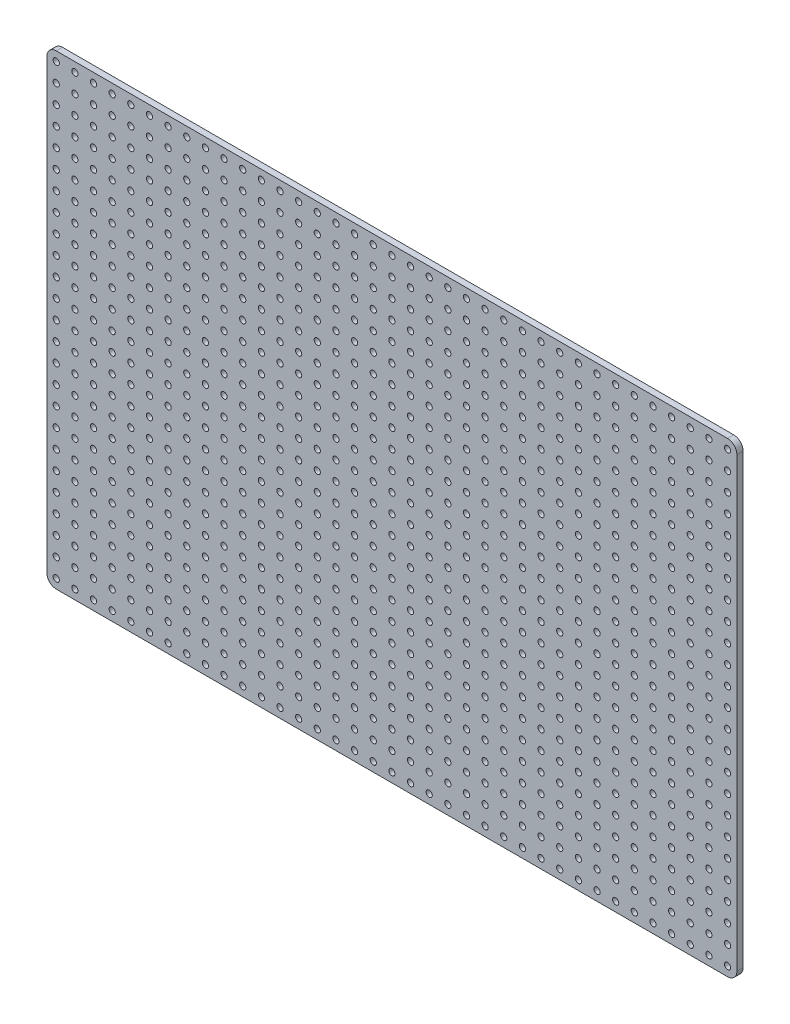
SolidWorks part; units mm, degrees
ref_plane "Alzado" through (0, 0, 0) normal (0, 0, 1) x (1, 0, 0)
ref_plane "Planta" through (0, 0, 0) normal (0, 1, 0) x (1, 0, 0)
ref_plane "Vista lateral" through (0, 0, 0) normal (1, 0, 0) x (0, 0, -1)
sketch "Model" plane through (0, 0, 0) normal (0, 0, 1) x (1, 0, 0)
  line L0 (256.4291, 471.7422) -> (580.4291, 471.7422)
  line L1 (256.4291, 246.7422) -> (580.4291, 246.7422)
  line L2 (251.9291, 251.2422) -> (251.9291, 467.2422)
  line L3 (584.9291, 467.2422) -> (584.9291, 251.2422)
  arc A0 (584.9291, 467.2422) -> (580.4291, 471.7422) centre (580.4291, 467.2422) ccw
  arc A1 (256.4291, 471.7422) -> (251.9291, 467.2422) centre (256.4291, 467.2422) ccw
  arc A2 (580.4291, 246.7422) -> (584.9291, 251.2422) centre (580.4291, 251.2422) ccw
  arc A3 (251.9291, 251.2422) -> (256.4291, 246.7422) centre (256.4291, 251.2422) ccw
  circle A4 centre (256.4291, 467.2422) radius 1.5
  circle A5 centre (256.4291, 458.2422) radius 1.5
  circle A6 centre (256.4291, 449.2422) radius 1.5
  circle A7 centre (256.4291, 440.2422) radius 1.5
  circle A8 centre (256.4291, 431.2422) radius 1.5
  circle A9 centre (256.4291, 422.2422) radius 1.5
  circle A10 centre (256.4291, 413.2422) radius 1.5
  circle A11 centre (256.4291, 404.2422) radius 1.5
  circle A12 centre (256.4291, 395.2422) radius 1.5
  circle A13 centre (256.4291, 386.2422) radius 1.5
  circle A14 centre (256.4291, 377.2422) radius 1.5
  circle A15 centre (256.4291, 368.2422) radius 1.5
  circle A16 centre (256.4291, 359.2422) radius 1.5
  circle A17 centre (256.4291, 350.2422) radius 1.5
  circle A18 centre (256.4291, 341.2422) radius 1.5
  circle A19 centre (256.4291, 332.2422) radius 1.5
  circle A20 centre (256.4291, 323.2422) radius 1.5
  circle A21 centre (256.4291, 314.2422) radius 1.5
  circle A22 centre (256.4291, 305.2422) radius 1.5
  circle A23 centre (265.4291, 467.2422) radius 1.5
  circle A24 centre (265.4291, 458.2422) radius 1.5
  circle A25 centre (265.4291, 449.2422) radius 1.5
  circle A26 centre (265.4291, 440.2422) radius 1.5
  circle A27 centre (265.4291, 431.2422) radius 1.5
  circle A28 centre (265.4291, 422.2422) radius 1.5
  circle A29 centre (265.4291, 413.2422) radius 1.5
  circle A30 centre (265.4291, 404.2422) radius 1.5
  circle A31 centre (265.4291, 395.2422) radius 1.5
  circle A32 centre (265.4291, 386.2422) radius 1.5
  circle A33 centre (265.4291, 377.2422) radius 1.5
  circle A34 centre (265.4291, 368.2422) radius 1.5
  circle A35 centre (265.4291, 359.2422) radius 1.5
  circle A36 centre (265.4291, 350.2422) radius 1.5
  circle A37 centre (265.4291, 341.2422) radius 1.5
  circle A38 centre (265.4291, 332.2422) radius 1.5
  circle A39 centre (265.4291, 323.2422) radius 1.5
  circle A40 centre (265.4291, 314.2422) radius 1.5
  circle A41 centre (265.4291, 305.2422) radius 1.5
  circle A42 centre (274.4291, 467.2422) radius 1.5
  circle A43 centre (274.4291, 458.2422) radius 1.5
  circle A44 centre (274.4291, 449.2422) radius 1.5
  circle A45 centre (274.4291, 440.2422) radius 1.5
  circle A46 centre (274.4291, 431.2422) radius 1.5
  circle A47 centre (274.4291, 422.2422) radius 1.5
  circle A48 centre (274.4291, 413.2422) radius 1.5
  circle A49 centre (274.4291, 404.2422) radius 1.5
  circle A50 centre (274.4291, 395.2422) radius 1.5
  circle A51 centre (274.4291, 386.2422) radius 1.5
  circle A52 centre (274.4291, 377.2422) radius 1.5
  circle A53 centre (274.4291, 368.2422) radius 1.5
  circle A54 centre (274.4291, 359.2422) radius 1.5
  circle A55 centre (274.4291, 350.2422) radius 1.5
  circle A56 centre (274.4291, 341.2422) radius 1.5
  circle A57 centre (274.4291, 332.2422) radius 1.5
  circle A58 centre (274.4291, 323.2422) radius 1.5
  circle A59 centre (274.4291, 314.2422) radius 1.5
  circle A60 centre (274.4291, 305.2422) radius 1.5
  circle A61 centre (283.4291, 467.2422) radius 1.5
  circle A62 centre (283.4291, 458.2422) radius 1.5
  circle A63 centre (283.4291, 449.2422) radius 1.5
  circle A64 centre (283.4291, 440.2422) radius 1.5
  circle A65 centre (283.4291, 431.2422) radius 1.5
  circle A66 centre (283.4291, 422.2422) radius 1.5
  circle A67 centre (283.4291, 413.2422) radius 1.5
  circle A68 centre (283.4291, 404.2422) radius 1.5
  circle A69 centre (283.4291, 395.2422) radius 1.5
  circle A70 centre (283.4291, 386.2422) radius 1.5
  circle A71 centre (283.4291, 377.2422) radius 1.5
  circle A72 centre (283.4291, 368.2422) radius 1.5
  circle A73 centre (283.4291, 359.2422) radius 1.5
  circle A74 centre (283.4291, 350.2422) radius 1.5
  circle A75 centre (283.4291, 341.2422) radius 1.5
  circle A76 centre (283.4291, 332.2422) radius 1.5
  circle A77 centre (283.4291, 323.2422) radius 1.5
  circle A78 centre (283.4291, 314.2422) radius 1.5
  circle A79 centre (283.4291, 305.2422) radius 1.5
  circle A80 centre (292.4291, 467.2422) radius 1.5
  circle A81 centre (292.4291, 458.2422) radius 1.5
  circle A82 centre (292.4291, 449.2422) radius 1.5
  circle A83 centre (292.4291, 440.2422) radius 1.5
  circle A84 centre (292.4291, 431.2422) radius 1.5
  circle A85 centre (292.4291, 422.2422) radius 1.5
  circle A86 centre (292.4291, 413.2422) radius 1.5
  circle A87 centre (292.4291, 404.2422) radius 1.5
  circle A88 centre (292.4291, 395.2422) radius 1.5
  circle A89 centre (292.4291, 386.2422) radius 1.5
  circle A90 centre (292.4291, 377.2422) radius 1.5
  circle A91 centre (292.4291, 368.2422) radius 1.5
  circle A92 centre (292.4291, 359.2422) radius 1.5
  circle A93 centre (292.4291, 350.2422) radius 1.5
  circle A94 centre (292.4291, 341.2422) radius 1.5
  circle A95 centre (292.4291, 332.2422) radius 1.5
  circle A96 centre (292.4291, 323.2422) radius 1.5
  circle A97 centre (292.4291, 314.2422) radius 1.5
  circle A98 centre (292.4291, 305.2422) radius 1.5
  circle A99 centre (301.4291, 467.2422) radius 1.5
  circle A100 centre (301.4291, 458.2422) radius 1.5
  circle A101 centre (301.4291, 449.2422) radius 1.5
  circle A102 centre (301.4291, 440.2422) radius 1.5
  circle A103 centre (301.4291, 431.2422) radius 1.5
  circle A104 centre (301.4291, 422.2422) radius 1.5
  circle A105 centre (301.4291, 413.2422) radius 1.5
  circle A106 centre (301.4291, 404.2422) radius 1.5
  circle A107 centre (301.4291, 395.2422) radius 1.5
  circle A108 centre (301.4291, 386.2422) radius 1.5
  circle A109 centre (301.4291, 377.2422) radius 1.5
  circle A110 centre (301.4291, 368.2422) radius 1.5
  circle A111 centre (301.4291, 359.2422) radius 1.5
  circle A112 centre (301.4291, 350.2422) radius 1.5
  circle A113 centre (301.4291, 341.2422) radius 1.5
  circle A114 centre (301.4291, 332.2422) radius 1.5
  circle A115 centre (301.4291, 323.2422) radius 1.5
  circle A116 centre (301.4291, 314.2422) radius 1.5
  circle A117 centre (301.4291, 305.2422) radius 1.5
  circle A118 centre (310.4291, 467.2422) radius 1.5
  circle A119 centre (310.4291, 458.2422) radius 1.5
  circle A120 centre (310.4291, 449.2422) radius 1.5
  circle A121 centre (310.4291, 440.2422) radius 1.5
  circle A122 centre (310.4291, 431.2422) radius 1.5
  circle A123 centre (310.4291, 422.2422) radius 1.5
  circle A124 centre (310.4291, 413.2422) radius 1.5
  circle A125 centre (310.4291, 404.2422) radius 1.5
  circle A126 centre (310.4291, 395.2422) radius 1.5
  circle A127 centre (310.4291, 386.2422) radius 1.5
  circle A128 centre (310.4291, 377.2422) radius 1.5
  circle A129 centre (310.4291, 368.2422) radius 1.5
  circle A130 centre (310.4291, 359.2422) radius 1.5
  circle A131 centre (310.4291, 350.2422) radius 1.5
  circle A132 centre (310.4291, 341.2422) radius 1.5
  circle A133 centre (310.4291, 332.2422) radius 1.5
  circle A134 centre (310.4291, 323.2422) radius 1.5
  circle A135 centre (310.4291, 314.2422) radius 1.5
  circle A136 centre (310.4291, 305.2422) radius 1.5
  circle A137 centre (319.4291, 467.2422) radius 1.5
  circle A138 centre (319.4291, 458.2422) radius 1.5
  circle A139 centre (319.4291, 449.2422) radius 1.5
  circle A140 centre (319.4291, 440.2422) radius 1.5
  circle A141 centre (319.4291, 431.2422) radius 1.5
  circle A142 centre (319.4291, 422.2422) radius 1.5
  circle A143 centre (319.4291, 413.2422) radius 1.5
  circle A144 centre (319.4291, 404.2422) radius 1.5
  circle A145 centre (319.4291, 395.2422) radius 1.5
  circle A146 centre (319.4291, 386.2422) radius 1.5
  circle A147 centre (319.4291, 377.2422) radius 1.5
  circle A148 centre (319.4291, 368.2422) radius 1.5
  circle A149 centre (319.4291, 359.2422) radius 1.5
  circle A150 centre (319.4291, 350.2422) radius 1.5
  circle A151 centre (319.4291, 341.2422) radius 1.5
  circle A152 centre (319.4291, 332.2422) radius 1.5
  circle A153 centre (319.4291, 323.2422) radius 1.5
  circle A154 centre (319.4291, 314.2422) radius 1.5
  circle A155 centre (319.4291, 305.2422) radius 1.5
  circle A156 centre (328.4291, 467.2422) radius 1.5
  circle A157 centre (328.4291, 458.2422) radius 1.5
  circle A158 centre (328.4291, 449.2422) radius 1.5
  circle A159 centre (328.4291, 440.2422) radius 1.5
  circle A160 centre (328.4291, 431.2422) radius 1.5
  circle A161 centre (328.4291, 422.2422) radius 1.5
  circle A162 centre (328.4291, 413.2422) radius 1.5
  circle A163 centre (328.4291, 404.2422) radius 1.5
  circle A164 centre (328.4291, 395.2422) radius 1.5
  circle A165 centre (328.4291, 386.2422) radius 1.5
  circle A166 centre (328.4291, 377.2422) radius 1.5
  circle A167 centre (328.4291, 368.2422) radius 1.5
  circle A168 centre (328.4291, 359.2422) radius 1.5
  circle A169 centre (328.4291, 350.2422) radius 1.5
  circle A170 centre (328.4291, 341.2422) radius 1.5
  circle A171 centre (328.4291, 332.2422) radius 1.5
  circle A172 centre (328.4291, 323.2422) radius 1.5
  circle A173 centre (328.4291, 314.2422) radius 1.5
  circle A174 centre (328.4291, 305.2422) radius 1.5
  circle A175 centre (337.4291, 467.2422) radius 1.5
  circle A176 centre (337.4291, 458.2422) radius 1.5
  circle A177 centre (337.4291, 449.2422) radius 1.5
  circle A178 centre (337.4291, 440.2422) radius 1.5
  circle A179 centre (337.4291, 431.2422) radius 1.5
  circle A180 centre (337.4291, 422.2422) radius 1.5
  circle A181 centre (337.4291, 413.2422) radius 1.5
  circle A182 centre (337.4291, 404.2422) radius 1.5
  circle A183 centre (337.4291, 395.2422) radius 1.5
  circle A184 centre (337.4291, 386.2422) radius 1.5
  circle A185 centre (337.4291, 377.2422) radius 1.5
  circle A186 centre (337.4291, 368.2422) radius 1.5
  circle A187 centre (337.4291, 359.2422) radius 1.5
  circle A188 centre (337.4291, 350.2422) radius 1.5
  circle A189 centre (337.4291, 341.2422) radius 1.5
  circle A190 centre (337.4291, 332.2422) radius 1.5
  circle A191 centre (337.4291, 323.2422) radius 1.5
  circle A192 centre (337.4291, 314.2422) radius 1.5
  circle A193 centre (337.4291, 305.2422) radius 1.5
  circle A194 centre (346.4291, 467.2422) radius 1.5
  circle A195 centre (346.4291, 458.2422) radius 1.5
  circle A196 centre (346.4291, 449.2422) radius 1.5
  circle A197 centre (346.4291, 440.2422) radius 1.5
  circle A198 centre (346.4291, 431.2422) radius 1.5
  circle A199 centre (346.4291, 422.2422) radius 1.5
  circle A200 centre (346.4291, 413.2422) radius 1.5
  circle A201 centre (346.4291, 404.2422) radius 1.5
  circle A202 centre (346.4291, 395.2422) radius 1.5
  circle A203 centre (346.4291, 386.2422) radius 1.5
  circle A204 centre (346.4291, 377.2422) radius 1.5
  circle A205 centre (346.4291, 368.2422) radius 1.5
  circle A206 centre (346.4291, 359.2422) radius 1.5
  circle A207 centre (346.4291, 350.2422) radius 1.5
  circle A208 centre (346.4291, 341.2422) radius 1.5
  circle A209 centre (346.4291, 332.2422) radius 1.5
  circle A210 centre (346.4291, 323.2422) radius 1.5
  circle A211 centre (346.4291, 314.2422) radius 1.5
  circle A212 centre (346.4291, 305.2422) radius 1.5
  circle A213 centre (355.4291, 467.2422) radius 1.5
  circle A214 centre (355.4291, 458.2422) radius 1.5
  circle A215 centre (355.4291, 449.2422) radius 1.5
  circle A216 centre (355.4291, 440.2422) radius 1.5
  circle A217 centre (355.4291, 431.2422) radius 1.5
  circle A218 centre (355.4291, 422.2422) radius 1.5
  circle A219 centre (355.4291, 413.2422) radius 1.5
  circle A220 centre (355.4291, 404.2422) radius 1.5
  circle A221 centre (355.4291, 395.2422) radius 1.5
  circle A222 centre (355.4291, 386.2422) radius 1.5
  circle A223 centre (355.4291, 377.2422) radius 1.5
  circle A224 centre (355.4291, 368.2422) radius 1.5
  circle A225 centre (355.4291, 359.2422) radius 1.5
  circle A226 centre (355.4291, 350.2422) radius 1.5
  circle A227 centre (355.4291, 341.2422) radius 1.5
  circle A228 centre (355.4291, 332.2422) radius 1.5
  circle A229 centre (355.4291, 323.2422) radius 1.5
  circle A230 centre (355.4291, 314.2422) radius 1.5
  circle A231 centre (355.4291, 305.2422) radius 1.5
  circle A232 centre (364.4291, 467.2422) radius 1.5
  circle A233 centre (364.4291, 458.2422) radius 1.5
  circle A234 centre (364.4291, 449.2422) radius 1.5
  circle A235 centre (364.4291, 440.2422) radius 1.5
  circle A236 centre (364.4291, 431.2422) radius 1.5
  circle A237 centre (364.4291, 422.2422) radius 1.5
  circle A238 centre (364.4291, 413.2422) radius 1.5
  circle A239 centre (364.4291, 404.2422) radius 1.5
  circle A240 centre (364.4291, 395.2422) radius 1.5
  circle A241 centre (364.4291, 386.2422) radius 1.5
  circle A242 centre (364.4291, 377.2422) radius 1.5
  circle A243 centre (364.4291, 368.2422) radius 1.5
  circle A244 centre (364.4291, 359.2422) radius 1.5
  circle A245 centre (364.4291, 350.2422) radius 1.5
  circle A246 centre (364.4291, 341.2422) radius 1.5
  circle A247 centre (364.4291, 332.2422) radius 1.5
  circle A248 centre (364.4291, 323.2422) radius 1.5
  circle A249 centre (364.4291, 314.2422) radius 1.5
  circle A250 centre (364.4291, 305.2422) radius 1.5
  circle A251 centre (373.4291, 467.2422) radius 1.5
  circle A252 centre (373.4291, 458.2422) radius 1.5
  circle A253 centre (373.4291, 449.2422) radius 1.5
  circle A254 centre (373.4291, 440.2422) radius 1.5
  circle A255 centre (373.4291, 431.2422) radius 1.5
  circle A256 centre (373.4291, 422.2422) radius 1.5
  circle A257 centre (373.4291, 413.2422) radius 1.5
  circle A258 centre (373.4291, 404.2422) radius 1.5
  circle A259 centre (373.4291, 395.2422) radius 1.5
  circle A260 centre (373.4291, 386.2422) radius 1.5
  circle A261 centre (373.4291, 377.2422) radius 1.5
  circle A262 centre (373.4291, 368.2422) radius 1.5
  circle A263 centre (373.4291, 359.2422) radius 1.5
  circle A264 centre (373.4291, 350.2422) radius 1.5
  circle A265 centre (373.4291, 341.2422) radius 1.5
  circle A266 centre (373.4291, 332.2422) radius 1.5
  circle A267 centre (373.4291, 323.2422) radius 1.5
  circle A268 centre (373.4291, 314.2422) radius 1.5
  circle A269 centre (373.4291, 305.2422) radius 1.5
  circle A270 centre (382.4291, 467.2422) radius 1.5
  circle A271 centre (382.4291, 458.2422) radius 1.5
  circle A272 centre (382.4291, 449.2422) radius 1.5
  circle A273 centre (382.4291, 440.2422) radius 1.5
  circle A274 centre (382.4291, 431.2422) radius 1.5
  circle A275 centre (382.4291, 422.2422) radius 1.5
  circle A276 centre (382.4291, 413.2422) radius 1.5
  circle A277 centre (382.4291, 404.2422) radius 1.5
  circle A278 centre (382.4291, 395.2422) radius 1.5
  circle A279 centre (382.4291, 386.2422) radius 1.5
  circle A280 centre (382.4291, 377.2422) radius 1.5
  circle A281 centre (382.4291, 368.2422) radius 1.5
  circle A282 centre (382.4291, 359.2422) radius 1.5
  circle A283 centre (382.4291, 350.2422) radius 1.5
  circle A284 centre (382.4291, 341.2422) radius 1.5
  circle A285 centre (382.4291, 332.2422) radius 1.5
  circle A286 centre (382.4291, 323.2422) radius 1.5
  circle A287 centre (382.4291, 314.2422) radius 1.5
  circle A288 centre (382.4291, 305.2422) radius 1.5
  circle A289 centre (391.4291, 467.2422) radius 1.5
  circle A290 centre (391.4291, 458.2422) radius 1.5
  circle A291 centre (391.4291, 449.2422) radius 1.5
  circle A292 centre (391.4291, 440.2422) radius 1.5
  circle A293 centre (391.4291, 431.2422) radius 1.5
  circle A294 centre (391.4291, 422.2422) radius 1.5
  circle A295 centre (391.4291, 413.2422) radius 1.5
  circle A296 centre (391.4291, 404.2422) radius 1.5
  circle A297 centre (391.4291, 395.2422) radius 1.5
  circle A298 centre (391.4291, 386.2422) radius 1.5
  circle A299 centre (391.4291, 377.2422) radius 1.5
  circle A300 centre (391.4291, 368.2422) radius 1.5
  circle A301 centre (391.4291, 359.2422) radius 1.5
  circle A302 centre (391.4291, 350.2422) radius 1.5
  circle A303 centre (391.4291, 341.2422) radius 1.5
  circle A304 centre (391.4291, 332.2422) radius 1.5
  circle A305 centre (391.4291, 323.2422) radius 1.5
  circle A306 centre (391.4291, 314.2422) radius 1.5
  circle A307 centre (391.4291, 305.2422) radius 1.5
  circle A308 centre (400.4291, 467.2422) radius 1.5
  circle A309 centre (400.4291, 458.2422) radius 1.5
  circle A310 centre (400.4291, 449.2422) radius 1.5
  circle A311 centre (400.4291, 440.2422) radius 1.5
  circle A312 centre (400.4291, 431.2422) radius 1.5
  circle A313 centre (400.4291, 422.2422) radius 1.5
  circle A314 centre (400.4291, 413.2422) radius 1.5
  circle A315 centre (400.4291, 404.2422) radius 1.5
  circle A316 centre (400.4291, 395.2422) radius 1.5
  circle A317 centre (400.4291, 386.2422) radius 1.5
  circle A318 centre (400.4291, 377.2422) radius 1.5
  circle A319 centre (400.4291, 368.2422) radius 1.5
  circle A320 centre (400.4291, 359.2422) radius 1.5
  circle A321 centre (400.4291, 350.2422) radius 1.5
  circle A322 centre (400.4291, 341.2422) radius 1.5
  circle A323 centre (400.4291, 332.2422) radius 1.5
  circle A324 centre (400.4291, 323.2422) radius 1.5
  circle A325 centre (400.4291, 314.2422) radius 1.5
  circle A326 centre (400.4291, 305.2422) radius 1.5
  circle A327 centre (409.4291, 467.2422) radius 1.5
  circle A328 centre (409.4291, 458.2422) radius 1.5
  circle A329 centre (409.4291, 449.2422) radius 1.5
  circle A330 centre (409.4291, 440.2422) radius 1.5
  circle A331 centre (409.4291, 431.2422) radius 1.5
  circle A332 centre (409.4291, 422.2422) radius 1.5
  circle A333 centre (409.4291, 413.2422) radius 1.5
  circle A334 centre (409.4291, 404.2422) radius 1.5
  circle A335 centre (409.4291, 395.2422) radius 1.5
  circle A336 centre (409.4291, 386.2422) radius 1.5
  circle A337 centre (409.4291, 377.2422) radius 1.5
  circle A338 centre (409.4291, 368.2422) radius 1.5
  circle A339 centre (409.4291, 359.2422) radius 1.5
  circle A340 centre (409.4291, 350.2422) radius 1.5
  circle A341 centre (409.4291, 341.2422) radius 1.5
  circle A342 centre (409.4291, 332.2422) radius 1.5
  circle A343 centre (409.4291, 323.2422) radius 1.5
  circle A344 centre (409.4291, 314.2422) radius 1.5
  circle A345 centre (409.4291, 305.2422) radius 1.5
  circle A346 centre (418.4291, 467.2422) radius 1.5
  circle A347 centre (418.4291, 458.2422) radius 1.5
  circle A348 centre (418.4291, 449.2422) radius 1.5
  circle A349 centre (418.4291, 440.2422) radius 1.5
  circle A350 centre (418.4291, 431.2422) radius 1.5
  circle A351 centre (418.4291, 422.2422) radius 1.5
  circle A352 centre (418.4291, 413.2422) radius 1.5
  circle A353 centre (418.4291, 404.2422) radius 1.5
  circle A354 centre (418.4291, 395.2422) radius 1.5
  circle A355 centre (418.4291, 386.2422) radius 1.5
  circle A356 centre (418.4291, 377.2422) radius 1.5
  circle A357 centre (418.4291, 368.2422) radius 1.5
  circle A358 centre (418.4291, 359.2422) radius 1.5
  circle A359 centre (418.4291, 350.2422) radius 1.5
  circle A360 centre (418.4291, 341.2422) radius 1.5
  circle A361 centre (418.4291, 332.2422) radius 1.5
  circle A362 centre (418.4291, 323.2422) radius 1.5
  circle A363 centre (418.4291, 314.2422) radius 1.5
  circle A364 centre (418.4291, 305.2422) radius 1.5
  circle A365 centre (427.4291, 467.2422) radius 1.5
  circle A366 centre (427.4291, 458.2422) radius 1.5
  circle A367 centre (427.4291, 449.2422) radius 1.5
  circle A368 centre (427.4291, 440.2422) radius 1.5
  circle A369 centre (427.4291, 431.2422) radius 1.5
  circle A370 centre (427.4291, 422.2422) radius 1.5
  circle A371 centre (427.4291, 413.2422) radius 1.5
  circle A372 centre (427.4291, 404.2422) radius 1.5
  circle A373 centre (427.4291, 395.2422) radius 1.5
  circle A374 centre (427.4291, 386.2422) radius 1.5
  circle A375 centre (427.4291, 377.2422) radius 1.5
  circle A376 centre (427.4291, 368.2422) radius 1.5
  circle A377 centre (427.4291, 359.2422) radius 1.5
  circle A378 centre (427.4291, 350.2422) radius 1.5
  circle A379 centre (427.4291, 341.2422) radius 1.5
  circle A380 centre (427.4291, 332.2422) radius 1.5
  circle A381 centre (427.4291, 323.2422) radius 1.5
  circle A382 centre (427.4291, 314.2422) radius 1.5
  circle A383 centre (427.4291, 305.2422) radius 1.5
  circle A384 centre (436.4291, 467.2422) radius 1.5
  circle A385 centre (436.4291, 458.2422) radius 1.5
  circle A386 centre (436.4291, 449.2422) radius 1.5
  circle A387 centre (436.4291, 440.2422) radius 1.5
  circle A388 centre (436.4291, 431.2422) radius 1.5
  circle A389 centre (436.4291, 422.2422) radius 1.5
  circle A390 centre (436.4291, 413.2422) radius 1.5
  circle A391 centre (436.4291, 404.2422) radius 1.5
  circle A392 centre (436.4291, 395.2422) radius 1.5
  circle A393 centre (436.4291, 386.2422) radius 1.5
  circle A394 centre (436.4291, 377.2422) radius 1.5
  circle A395 centre (436.4291, 368.2422) radius 1.5
  circle A396 centre (436.4291, 359.2422) radius 1.5
  circle A397 centre (436.4291, 350.2422) radius 1.5
  circle A398 centre (436.4291, 341.2422) radius 1.5
  circle A399 centre (436.4291, 332.2422) radius 1.5
  circle A400 centre (436.4291, 323.2422) radius 1.5
  circle A401 centre (436.4291, 314.2422) radius 1.5
  circle A402 centre (436.4291, 305.2422) radius 1.5
  circle A403 centre (445.4291, 467.2422) radius 1.5
  circle A404 centre (445.4291, 458.2422) radius 1.5
  circle A405 centre (445.4291, 449.2422) radius 1.5
  circle A406 centre (445.4291, 440.2422) radius 1.5
  circle A407 centre (445.4291, 431.2422) radius 1.5
  circle A408 centre (445.4291, 422.2422) radius 1.5
  circle A409 centre (445.4291, 413.2422) radius 1.5
  circle A410 centre (445.4291, 404.2422) radius 1.5
  circle A411 centre (445.4291, 395.2422) radius 1.5
  circle A412 centre (445.4291, 386.2422) radius 1.5
  circle A413 centre (445.4291, 377.2422) radius 1.5
  circle A414 centre (445.4291, 368.2422) radius 1.5
  circle A415 centre (445.4291, 359.2422) radius 1.5
  circle A416 centre (445.4291, 350.2422) radius 1.5
  circle A417 centre (445.4291, 341.2422) radius 1.5
  circle A418 centre (445.4291, 332.2422) radius 1.5
  circle A419 centre (445.4291, 323.2422) radius 1.5
  circle A420 centre (445.4291, 314.2422) radius 1.5
  circle A421 centre (445.4291, 305.2422) radius 1.5
  circle A422 centre (454.4291, 467.2422) radius 1.5
  circle A423 centre (454.4291, 458.2422) radius 1.5
  circle A424 centre (454.4291, 449.2422) radius 1.5
  circle A425 centre (454.4291, 440.2422) radius 1.5
  circle A426 centre (454.4291, 431.2422) radius 1.5
  circle A427 centre (454.4291, 422.2422) radius 1.5
  circle A428 centre (454.4291, 413.2422) radius 1.5
  circle A429 centre (454.4291, 404.2422) radius 1.5
  circle A430 centre (454.4291, 395.2422) radius 1.5
  circle A431 centre (454.4291, 386.2422) radius 1.5
  circle A432 centre (454.4291, 377.2422) radius 1.5
  circle A433 centre (454.4291, 368.2422) radius 1.5
  circle A434 centre (454.4291, 359.2422) radius 1.5
  circle A435 centre (454.4291, 350.2422) radius 1.5
  circle A436 centre (454.4291, 341.2422) radius 1.5
  circle A437 centre (454.4291, 332.2422) radius 1.5
  circle A438 centre (454.4291, 323.2422) radius 1.5
  circle A439 centre (454.4291, 314.2422) radius 1.5
  circle A440 centre (454.4291, 305.2422) radius 1.5
  circle A441 centre (463.4291, 467.2422) radius 1.5
  circle A442 centre (463.4291, 458.2422) radius 1.5
  circle A443 centre (463.4291, 449.2422) radius 1.5
  circle A444 centre (463.4291, 440.2422) radius 1.5
  circle A445 centre (463.4291, 431.2422) radius 1.5
  circle A446 centre (463.4291, 422.2422) radius 1.5
  circle A447 centre (463.4291, 413.2422) radius 1.5
  circle A448 centre (463.4291, 404.2422) radius 1.5
  circle A449 centre (463.4291, 395.2422) radius 1.5
  circle A450 centre (463.4291, 386.2422) radius 1.5
  circle A451 centre (463.4291, 377.2422) radius 1.5
  circle A452 centre (463.4291, 368.2422) radius 1.5
  circle A453 centre (463.4291, 359.2422) radius 1.5
  circle A454 centre (463.4291, 350.2422) radius 1.5
  circle A455 centre (463.4291, 341.2422) radius 1.5
  circle A456 centre (463.4291, 332.2422) radius 1.5
  circle A457 centre (463.4291, 323.2422) radius 1.5
  circle A458 centre (463.4291, 314.2422) radius 1.5
  circle A459 centre (463.4291, 305.2422) radius 1.5
  circle A460 centre (472.4291, 467.2422) radius 1.5
  circle A461 centre (472.4291, 458.2422) radius 1.5
  circle A462 centre (472.4291, 449.2422) radius 1.5
  circle A463 centre (472.4291, 440.2422) radius 1.5
  circle A464 centre (472.4291, 431.2422) radius 1.5
  circle A465 centre (472.4291, 422.2422) radius 1.5
  circle A466 centre (472.4291, 413.2422) radius 1.5
  circle A467 centre (472.4291, 404.2422) radius 1.5
  circle A468 centre (472.4291, 395.2422) radius 1.5
  circle A469 centre (472.4291, 386.2422) radius 1.5
  circle A470 centre (472.4291, 377.2422) radius 1.5
  circle A471 centre (472.4291, 368.2422) radius 1.5
  circle A472 centre (472.4291, 359.2422) radius 1.5
  circle A473 centre (472.4291, 350.2422) radius 1.5
  circle A474 centre (472.4291, 341.2422) radius 1.5
  circle A475 centre (472.4291, 332.2422) radius 1.5
  circle A476 centre (472.4291, 323.2422) radius 1.5
  circle A477 centre (472.4291, 314.2422) radius 1.5
  circle A478 centre (472.4291, 305.2422) radius 1.5
  circle A479 centre (481.4291, 467.2422) radius 1.5
  circle A480 centre (481.4291, 458.2422) radius 1.5
  circle A481 centre (481.4291, 449.2422) radius 1.5
  circle A482 centre (481.4291, 440.2422) radius 1.5
  circle A483 centre (481.4291, 431.2422) radius 1.5
  circle A484 centre (481.4291, 422.2422) radius 1.5
  circle A485 centre (481.4291, 413.2422) radius 1.5
  circle A486 centre (481.4291, 404.2422) radius 1.5
  circle A487 centre (481.4291, 395.2422) radius 1.5
  circle A488 centre (481.4291, 386.2422) radius 1.5
  circle A489 centre (481.4291, 377.2422) radius 1.5
  circle A490 centre (481.4291, 368.2422) radius 1.5
  circle A491 centre (481.4291, 359.2422) radius 1.5
  circle A492 centre (481.4291, 350.2422) radius 1.5
  circle A493 centre (481.4291, 341.2422) radius 1.5
  circle A494 centre (481.4291, 332.2422) radius 1.5
  circle A495 centre (481.4291, 323.2422) radius 1.5
  circle A496 centre (481.4291, 314.2422) radius 1.5
  circle A497 centre (481.4291, 305.2422) radius 1.5
  circle A498 centre (490.4291, 467.2422) radius 1.5
  circle A499 centre (490.4291, 458.2422) radius 1.5
  circle A500 centre (490.4291, 449.2422) radius 1.5
  circle A501 centre (490.4291, 440.2422) radius 1.5
  circle A502 centre (490.4291, 431.2422) radius 1.5
  circle A503 centre (490.4291, 422.2422) radius 1.5
  circle A504 centre (490.4291, 413.2422) radius 1.5
  circle A505 centre (490.4291, 404.2422) radius 1.5
  circle A506 centre (490.4291, 395.2422) radius 1.5
  circle A507 centre (490.4291, 386.2422) radius 1.5
  circle A508 centre (490.4291, 377.2422) radius 1.5
  circle A509 centre (490.4291, 368.2422) radius 1.5
  circle A510 centre (490.4291, 359.2422) radius 1.5
  circle A511 centre (490.4291, 350.2422) radius 1.5
  circle A512 centre (490.4291, 341.2422) radius 1.5
  circle A513 centre (490.4291, 332.2422) radius 1.5
  circle A514 centre (490.4291, 323.2422) radius 1.5
  circle A515 centre (490.4291, 314.2422) radius 1.5
  circle A516 centre (490.4291, 305.2422) radius 1.5
  circle A517 centre (499.4291, 467.2422) radius 1.5
  circle A518 centre (499.4291, 458.2422) radius 1.5
  circle A519 centre (499.4291, 449.2422) radius 1.5
  circle A520 centre (499.4291, 440.2422) radius 1.5
  circle A521 centre (499.4291, 431.2422) radius 1.5
  circle A522 centre (499.4291, 422.2422) radius 1.5
  circle A523 centre (499.4291, 413.2422) radius 1.5
  circle A524 centre (499.4291, 404.2422) radius 1.5
  circle A525 centre (499.4291, 395.2422) radius 1.5
  circle A526 centre (499.4291, 386.2422) radius 1.5
  circle A527 centre (499.4291, 377.2422) radius 1.5
  circle A528 centre (499.4291, 368.2422) radius 1.5
  circle A529 centre (499.4291, 359.2422) radius 1.5
  circle A530 centre (499.4291, 350.2422) radius 1.5
  circle A531 centre (499.4291, 341.2422) radius 1.5
  circle A532 centre (499.4291, 332.2422) radius 1.5
  circle A533 centre (499.4291, 323.2422) radius 1.5
  circle A534 centre (499.4291, 314.2422) radius 1.5
  circle A535 centre (499.4291, 305.2422) radius 1.5
  circle A536 centre (508.4291, 467.2422) radius 1.5
  circle A537 centre (508.4291, 458.2422) radius 1.5
  circle A538 centre (508.4291, 449.2422) radius 1.5
  circle A539 centre (508.4291, 440.2422) radius 1.5
  circle A540 centre (508.4291, 431.2422) radius 1.5
  circle A541 centre (508.4291, 422.2422) radius 1.5
  circle A542 centre (508.4291, 413.2422) radius 1.5
  circle A543 centre (508.4291, 404.2422) radius 1.5
  circle A544 centre (508.4291, 395.2422) radius 1.5
  circle A545 centre (508.4291, 386.2422) radius 1.5
  circle A546 centre (508.4291, 377.2422) radius 1.5
  circle A547 centre (508.4291, 368.2422) radius 1.5
  circle A548 centre (508.4291, 359.2422) radius 1.5
  circle A549 centre (508.4291, 350.2422) radius 1.5
  circle A550 centre (508.4291, 341.2422) radius 1.5
  circle A551 centre (508.4291, 332.2422) radius 1.5
  circle A552 centre (508.4291, 323.2422) radius 1.5
  circle A553 centre (508.4291, 314.2422) radius 1.5
  circle A554 centre (508.4291, 305.2422) radius 1.5
  circle A555 centre (517.4291, 467.2422) radius 1.5
  circle A556 centre (517.4291, 458.2422) radius 1.5
  circle A557 centre (517.4291, 449.2422) radius 1.5
  circle A558 centre (517.4291, 440.2422) radius 1.5
  circle A559 centre (517.4291, 431.2422) radius 1.5
  circle A560 centre (517.4291, 422.2422) radius 1.5
  circle A561 centre (517.4291, 413.2422) radius 1.5
  circle A562 centre (517.4291, 404.2422) radius 1.5
  circle A563 centre (517.4291, 395.2422) radius 1.5
  circle A564 centre (517.4291, 386.2422) radius 1.5
  circle A565 centre (517.4291, 377.2422) radius 1.5
  circle A566 centre (517.4291, 368.2422) radius 1.5
  circle A567 centre (517.4291, 359.2422) radius 1.5
  circle A568 centre (517.4291, 350.2422) radius 1.5
  circle A569 centre (517.4291, 341.2422) radius 1.5
  circle A570 centre (517.4291, 332.2422) radius 1.5
  circle A571 centre (517.4291, 323.2422) radius 1.5
  circle A572 centre (517.4291, 314.2422) radius 1.5
  circle A573 centre (517.4291, 305.2422) radius 1.5
  circle A574 centre (256.4291, 296.2422) radius 1.5
  circle A575 centre (256.4291, 287.2422) radius 1.5
  circle A576 centre (256.4291, 278.2422) radius 1.5
  circle A577 centre (265.4291, 296.2422) radius 1.5
  circle A578 centre (265.4291, 287.2422) radius 1.5
  circle A579 centre (265.4291, 278.2422) radius 1.5
  circle A580 centre (274.4291, 296.2422) radius 1.5
  circle A581 centre (274.4291, 287.2422) radius 1.5
  circle A582 centre (274.4291, 278.2422) radius 1.5
  circle A583 centre (283.4291, 296.2422) radius 1.5
  circle A584 centre (283.4291, 287.2422) radius 1.5
  circle A585 centre (283.4291, 278.2422) radius 1.5
  circle A586 centre (292.4291, 296.2422) radius 1.5
  circle A587 centre (292.4291, 287.2422) radius 1.5
  circle A588 centre (292.4291, 278.2422) radius 1.5
  circle A589 centre (301.4291, 296.2422) radius 1.5
  circle A590 centre (301.4291, 287.2422) radius 1.5
  circle A591 centre (301.4291, 278.2422) radius 1.5
  circle A592 centre (310.4291, 296.2422) radius 1.5
  circle A593 centre (310.4291, 287.2422) radius 1.5
  circle A594 centre (310.4291, 278.2422) radius 1.5
  circle A595 centre (319.4291, 296.2422) radius 1.5
  circle A596 centre (319.4291, 287.2422) radius 1.5
  circle A597 centre (319.4291, 278.2422) radius 1.5
  circle A598 centre (328.4291, 296.2422) radius 1.5
  circle A599 centre (328.4291, 287.2422) radius 1.5
  circle A600 centre (328.4291, 278.2422) radius 1.5
  circle A601 centre (337.4291, 296.2422) radius 1.5
  circle A602 centre (337.4291, 287.2422) radius 1.5
  circle A603 centre (337.4291, 278.2422) radius 1.5
  circle A604 centre (346.4291, 296.2422) radius 1.5
  circle A605 centre (346.4291, 287.2422) radius 1.5
  circle A606 centre (346.4291, 278.2422) radius 1.5
  circle A607 centre (355.4291, 296.2422) radius 1.5
  circle A608 centre (355.4291, 287.2422) radius 1.5
  circle A609 centre (355.4291, 278.2422) radius 1.5
  circle A610 centre (364.4291, 296.2422) radius 1.5
  circle A611 centre (364.4291, 287.2422) radius 1.5
  circle A612 centre (364.4291, 278.2422) radius 1.5
  circle A613 centre (373.4291, 296.2422) radius 1.5
  circle A614 centre (373.4291, 287.2422) radius 1.5
  circle A615 centre (373.4291, 278.2422) radius 1.5
  circle A616 centre (382.4291, 296.2422) radius 1.5
  circle A617 centre (382.4291, 287.2422) radius 1.5
  circle A618 centre (382.4291, 278.2422) radius 1.5
  circle A619 centre (391.4291, 296.2422) radius 1.5
  circle A620 centre (391.4291, 287.2422) radius 1.5
  circle A621 centre (391.4291, 278.2422) radius 1.5
  circle A622 centre (400.4291, 296.2422) radius 1.5
  circle A623 centre (400.4291, 287.2422) radius 1.5
  circle A624 centre (400.4291, 278.2422) radius 1.5
  circle A625 centre (409.4291, 296.2422) radius 1.5
  circle A626 centre (409.4291, 287.2422) radius 1.5
  circle A627 centre (409.4291, 278.2422) radius 1.5
  circle A628 centre (418.4291, 296.2422) radius 1.5
  circle A629 centre (418.4291, 287.2422) radius 1.5
  circle A630 centre (418.4291, 278.2422) radius 1.5
  circle A631 centre (427.4291, 296.2422) radius 1.5
  circle A632 centre (427.4291, 287.2422) radius 1.5
  circle A633 centre (427.4291, 278.2422) radius 1.5
  circle A634 centre (436.4291, 296.2422) radius 1.5
  circle A635 centre (436.4291, 287.2422) radius 1.5
  circle A636 centre (436.4291, 278.2422) radius 1.5
  circle A637 centre (445.4291, 296.2422) radius 1.5
  circle A638 centre (445.4291, 287.2422) radius 1.5
  circle A639 centre (445.4291, 278.2422) radius 1.5
  circle A640 centre (454.4291, 296.2422) radius 1.5
  circle A641 centre (454.4291, 287.2422) radius 1.5
  circle A642 centre (454.4291, 278.2422) radius 1.5
  circle A643 centre (463.4291, 296.2422) radius 1.5
  circle A644 centre (463.4291, 287.2422) radius 1.5
  circle A645 centre (463.4291, 278.2422) radius 1.5
  circle A646 centre (472.4291, 296.2422) radius 1.5
  circle A647 centre (472.4291, 287.2422) radius 1.5
  circle A648 centre (472.4291, 278.2422) radius 1.5
  circle A649 centre (481.4291, 296.2422) radius 1.5
  circle A650 centre (481.4291, 287.2422) radius 1.5
  circle A651 centre (481.4291, 278.2422) radius 1.5
  circle A652 centre (490.4291, 296.2422) radius 1.5
  circle A653 centre (490.4291, 287.2422) radius 1.5
  circle A654 centre (490.4291, 278.2422) radius 1.5
  circle A655 centre (499.4291, 296.2422) radius 1.5
  circle A656 centre (499.4291, 287.2422) radius 1.5
  circle A657 centre (499.4291, 278.2422) radius 1.5
  circle A658 centre (508.4291, 296.2422) radius 1.5
  circle A659 centre (508.4291, 287.2422) radius 1.5
  circle A660 centre (508.4291, 278.2422) radius 1.5
  circle A661 centre (517.4291, 296.2422) radius 1.5
  circle A662 centre (517.4291, 287.2422) radius 1.5
  circle A663 centre (517.4291, 278.2422) radius 1.5
  circle A664 centre (256.4291, 269.2422) radius 1.5
  circle A665 centre (256.4291, 260.2422) radius 1.5
  circle A666 centre (256.4291, 251.2422) radius 1.5
  circle A667 centre (265.4291, 269.2422) radius 1.5
  circle A668 centre (265.4291, 260.2422) radius 1.5
  circle A669 centre (265.4291, 251.2422) radius 1.5
  circle A670 centre (274.4291, 269.2422) radius 1.5
  circle A671 centre (274.4291, 260.2422) radius 1.5
  circle A672 centre (274.4291, 251.2422) radius 1.5
  circle A673 centre (283.4291, 269.2422) radius 1.5
  circle A674 centre (283.4291, 260.2422) radius 1.5
  circle A675 centre (283.4291, 251.2422) radius 1.5
  circle A676 centre (292.4291, 269.2422) radius 1.5
  circle A677 centre (292.4291, 260.2422) radius 1.5
  circle A678 centre (292.4291, 251.2422) radius 1.5
  circle A679 centre (301.4291, 269.2422) radius 1.5
  circle A680 centre (301.4291, 260.2422) radius 1.5
  circle A681 centre (301.4291, 251.2422) radius 1.5
  circle A682 centre (310.4291, 269.2422) radius 1.5
  circle A683 centre (310.4291, 260.2422) radius 1.5
  circle A684 centre (310.4291, 251.2422) radius 1.5
  circle A685 centre (319.4291, 269.2422) radius 1.5
  circle A686 centre (319.4291, 260.2422) radius 1.5
  circle A687 centre (319.4291, 251.2422) radius 1.5
  circle A688 centre (328.4291, 269.2422) radius 1.5
  circle A689 centre (328.4291, 260.2422) radius 1.5
  circle A690 centre (328.4291, 251.2422) radius 1.5
  circle A691 centre (337.4291, 269.2422) radius 1.5
  circle A692 centre (337.4291, 260.2422) radius 1.5
  circle A693 centre (337.4291, 251.2422) radius 1.5
  circle A694 centre (346.4291, 269.2422) radius 1.5
  circle A695 centre (346.4291, 260.2422) radius 1.5
  circle A696 centre (346.4291, 251.2422) radius 1.5
  circle A697 centre (355.4291, 269.2422) radius 1.5
  circle A698 centre (355.4291, 260.2422) radius 1.5
  circle A699 centre (355.4291, 251.2422) radius 1.5
  circle A700 centre (364.4291, 269.2422) radius 1.5
  circle A701 centre (364.4291, 260.2422) radius 1.5
  circle A702 centre (364.4291, 251.2422) radius 1.5
  circle A703 centre (373.4291, 269.2422) radius 1.5
  circle A704 centre (373.4291, 260.2422) radius 1.5
  circle A705 centre (373.4291, 251.2422) radius 1.5
  circle A706 centre (382.4291, 269.2422) radius 1.5
  circle A707 centre (382.4291, 260.2422) radius 1.5
  circle A708 centre (382.4291, 251.2422) radius 1.5
  circle A709 centre (391.4291, 269.2422) radius 1.5
  circle A710 centre (391.4291, 260.2422) radius 1.5
  circle A711 centre (391.4291, 251.2422) radius 1.5
  circle A712 centre (400.4291, 269.2422) radius 1.5
  circle A713 centre (400.4291, 260.2422) radius 1.5
  circle A714 centre (400.4291, 251.2422) radius 1.5
  circle A715 centre (409.4291, 269.2422) radius 1.5
  circle A716 centre (409.4291, 260.2422) radius 1.5
  circle A717 centre (409.4291, 251.2422) radius 1.5
  circle A718 centre (418.4291, 269.2422) radius 1.5
  circle A719 centre (418.4291, 260.2422) radius 1.5
  circle A720 centre (418.4291, 251.2422) radius 1.5
  circle A721 centre (427.4291, 269.2422) radius 1.5
  circle A722 centre (427.4291, 260.2422) radius 1.5
  circle A723 centre (427.4291, 251.2422) radius 1.5
  circle A724 centre (436.4291, 269.2422) radius 1.5
  circle A725 centre (436.4291, 260.2422) radius 1.5
  circle A726 centre (436.4291, 251.2422) radius 1.5
  circle A727 centre (445.4291, 269.2422) radius 1.5
  circle A728 centre (445.4291, 260.2422) radius 1.5
  circle A729 centre (445.4291, 251.2422) radius 1.5
  circle A730 centre (454.4291, 269.2422) radius 1.5
  circle A731 centre (454.4291, 260.2422) radius 1.5
  circle A732 centre (454.4291, 251.2422) radius 1.5
  circle A733 centre (463.4291, 269.2422) radius 1.5
  circle A734 centre (463.4291, 260.2422) radius 1.5
  circle A735 centre (463.4291, 251.2422) radius 1.5
  circle A736 centre (472.4291, 269.2422) radius 1.5
  circle A737 centre (472.4291, 260.2422) radius 1.5
  circle A738 centre (472.4291, 251.2422) radius 1.5
  circle A739 centre (481.4291, 269.2422) radius 1.5
  circle A740 centre (481.4291, 260.2422) radius 1.5
  circle A741 centre (481.4291, 251.2422) radius 1.5
  circle A742 centre (490.4291, 269.2422) radius 1.5
  circle A743 centre (490.4291, 260.2422) radius 1.5
  circle A744 centre (490.4291, 251.2422) radius 1.5
  circle A745 centre (499.4291, 269.2422) radius 1.5
  circle A746 centre (499.4291, 260.2422) radius 1.5
  circle A747 centre (499.4291, 251.2422) radius 1.5
  circle A748 centre (508.4291, 269.2422) radius 1.5
  circle A749 centre (508.4291, 260.2422) radius 1.5
  circle A750 centre (508.4291, 251.2422) radius 1.5
  circle A751 centre (517.4291, 269.2422) radius 1.5
  circle A752 centre (517.4291, 260.2422) radius 1.5
  circle A753 centre (517.4291, 251.2422) radius 1.5
  circle A754 centre (526.4291, 467.2422) radius 1.5
  circle A755 centre (526.4291, 458.2422) radius 1.5
  circle A756 centre (526.4291, 449.2422) radius 1.5
  circle A757 centre (526.4291, 440.2422) radius 1.5
  circle A758 centre (526.4291, 431.2422) radius 1.5
  circle A759 centre (526.4291, 422.2422) radius 1.5
  circle A760 centre (526.4291, 413.2422) radius 1.5
  circle A761 centre (526.4291, 404.2422) radius 1.5
  circle A762 centre (526.4291, 395.2422) radius 1.5
  circle A763 centre (526.4291, 386.2422) radius 1.5
  circle A764 centre (526.4291, 377.2422) radius 1.5
  circle A765 centre (526.4291, 368.2422) radius 1.5
  circle A766 centre (526.4291, 359.2422) radius 1.5
  circle A767 centre (526.4291, 350.2422) radius 1.5
  circle A768 centre (526.4291, 341.2422) radius 1.5
  circle A769 centre (526.4291, 332.2422) radius 1.5
  circle A770 centre (526.4291, 323.2422) radius 1.5
  circle A771 centre (526.4291, 314.2422) radius 1.5
  circle A772 centre (526.4291, 305.2422) radius 1.5
  circle A773 centre (535.4291, 467.2422) radius 1.5
  circle A774 centre (535.4291, 458.2422) radius 1.5
  circle A775 centre (535.4291, 449.2422) radius 1.5
  circle A776 centre (535.4291, 440.2422) radius 1.5
  circle A777 centre (535.4291, 431.2422) radius 1.5
  circle A778 centre (535.4291, 422.2422) radius 1.5
  circle A779 centre (535.4291, 413.2422) radius 1.5
  circle A780 centre (535.4291, 404.2422) radius 1.5
  circle A781 centre (535.4291, 395.2422) radius 1.5
  circle A782 centre (535.4291, 386.2422) radius 1.5
  circle A783 centre (535.4291, 377.2422) radius 1.5
  circle A784 centre (535.4291, 368.2422) radius 1.5
  circle A785 centre (535.4291, 359.2422) radius 1.5
  circle A786 centre (535.4291, 350.2422) radius 1.5
  circle A787 centre (535.4291, 341.2422) radius 1.5
  circle A788 centre (535.4291, 332.2422) radius 1.5
  circle A789 centre (535.4291, 323.2422) radius 1.5
  circle A790 centre (535.4291, 314.2422) radius 1.5
  circle A791 centre (535.4291, 305.2422) radius 1.5
  circle A792 centre (544.4291, 467.2422) radius 1.5
  circle A793 centre (544.4291, 458.2422) radius 1.5
  circle A794 centre (544.4291, 449.2422) radius 1.5
  circle A795 centre (544.4291, 440.2422) radius 1.5
  circle A796 centre (544.4291, 431.2422) radius 1.5
  circle A797 centre (544.4291, 422.2422) radius 1.5
  circle A798 centre (544.4291, 413.2422) radius 1.5
  circle A799 centre (544.4291, 404.2422) radius 1.5
  circle A800 centre (544.4291, 395.2422) radius 1.5
  circle A801 centre (544.4291, 386.2422) radius 1.5
  circle A802 centre (544.4291, 377.2422) radius 1.5
  circle A803 centre (544.4291, 368.2422) radius 1.5
  circle A804 centre (544.4291, 359.2422) radius 1.5
  circle A805 centre (544.4291, 350.2422) radius 1.5
  circle A806 centre (544.4291, 341.2422) radius 1.5
  circle A807 centre (544.4291, 332.2422) radius 1.5
  circle A808 centre (544.4291, 323.2422) radius 1.5
  circle A809 centre (544.4291, 314.2422) radius 1.5
  circle A810 centre (544.4291, 305.2422) radius 1.5
  circle A811 centre (553.4291, 467.2422) radius 1.5
  circle A812 centre (553.4291, 458.2422) radius 1.5
  circle A813 centre (553.4291, 449.2422) radius 1.5
  circle A814 centre (553.4291, 440.2422) radius 1.5
  circle A815 centre (553.4291, 431.2422) radius 1.5
  circle A816 centre (553.4291, 422.2422) radius 1.5
  circle A817 centre (553.4291, 413.2422) radius 1.5
  circle A818 centre (553.4291, 404.2422) radius 1.5
  circle A819 centre (553.4291, 395.2422) radius 1.5
  circle A820 centre (553.4291, 386.2422) radius 1.5
  circle A821 centre (553.4291, 377.2422) radius 1.5
  circle A822 centre (553.4291, 368.2422) radius 1.5
  circle A823 centre (553.4291, 359.2422) radius 1.5
  circle A824 centre (553.4291, 350.2422) radius 1.5
  circle A825 centre (553.4291, 341.2422) radius 1.5
  circle A826 centre (553.4291, 332.2422) radius 1.5
  circle A827 centre (553.4291, 323.2422) radius 1.5
  circle A828 centre (553.4291, 314.2422) radius 1.5
  circle A829 centre (553.4291, 305.2422) radius 1.5
  circle A830 centre (562.4291, 467.2422) radius 1.5
  circle A831 centre (562.4291, 458.2422) radius 1.5
  circle A832 centre (562.4291, 449.2422) radius 1.5
  circle A833 centre (562.4291, 440.2422) radius 1.5
  circle A834 centre (562.4291, 431.2422) radius 1.5
  circle A835 centre (562.4291, 422.2422) radius 1.5
  circle A836 centre (562.4291, 413.2422) radius 1.5
  circle A837 centre (562.4291, 404.2422) radius 1.5
  circle A838 centre (562.4291, 395.2422) radius 1.5
  circle A839 centre (562.4291, 386.2422) radius 1.5
  circle A840 centre (562.4291, 377.2422) radius 1.5
  circle A841 centre (562.4291, 368.2422) radius 1.5
  circle A842 centre (562.4291, 359.2422) radius 1.5
  circle A843 centre (562.4291, 350.2422) radius 1.5
  circle A844 centre (562.4291, 341.2422) radius 1.5
  circle A845 centre (562.4291, 332.2422) radius 1.5
  circle A846 centre (562.4291, 323.2422) radius 1.5
  circle A847 centre (562.4291, 314.2422) radius 1.5
  circle A848 centre (562.4291, 305.2422) radius 1.5
  circle A849 centre (526.4291, 296.2422) radius 1.5
  circle A850 centre (526.4291, 287.2422) radius 1.5
  circle A851 centre (526.4291, 278.2422) radius 1.5
  circle A852 centre (535.4291, 296.2422) radius 1.5
  circle A853 centre (535.4291, 287.2422) radius 1.5
  circle A854 centre (535.4291, 278.2422) radius 1.5
  circle A855 centre (544.4291, 296.2422) radius 1.5
  circle A856 centre (544.4291, 287.2422) radius 1.5
  circle A857 centre (544.4291, 278.2422) radius 1.5
  circle A858 centre (553.4291, 296.2422) radius 1.5
  circle A859 centre (553.4291, 287.2422) radius 1.5
  circle A860 centre (553.4291, 278.2422) radius 1.5
  circle A861 centre (562.4291, 296.2422) radius 1.5
  circle A862 centre (562.4291, 287.2422) radius 1.5
  circle A863 centre (562.4291, 278.2422) radius 1.5
  circle A864 centre (526.4291, 269.2422) radius 1.5
  circle A865 centre (526.4291, 260.2422) radius 1.5
  circle A866 centre (526.4291, 251.2422) radius 1.5
  circle A867 centre (535.4291, 269.2422) radius 1.5
  circle A868 centre (535.4291, 260.2422) radius 1.5
  circle A869 centre (535.4291, 251.2422) radius 1.5
  circle A870 centre (544.4291, 269.2422) radius 1.5
  circle A871 centre (544.4291, 260.2422) radius 1.5
  circle A872 centre (544.4291, 251.2422) radius 1.5
  circle A873 centre (553.4291, 269.2422) radius 1.5
  circle A874 centre (553.4291, 260.2422) radius 1.5
  circle A875 centre (553.4291, 251.2422) radius 1.5
  circle A876 centre (562.4291, 269.2422) radius 1.5
  circle A877 centre (562.4291, 260.2422) radius 1.5
  circle A878 centre (562.4291, 251.2422) radius 1.5
  circle A879 centre (571.4291, 467.2422) radius 1.5
  circle A880 centre (571.4291, 458.2422) radius 1.5
  circle A881 centre (571.4291, 449.2422) radius 1.5
  circle A882 centre (571.4291, 440.2422) radius 1.5
  circle A883 centre (571.4291, 431.2422) radius 1.5
  circle A884 centre (571.4291, 422.2422) radius 1.5
  circle A885 centre (571.4291, 413.2422) radius 1.5
  circle A886 centre (571.4291, 404.2422) radius 1.5
  circle A887 centre (571.4291, 395.2422) radius 1.5
  circle A888 centre (571.4291, 386.2422) radius 1.5
  circle A889 centre (571.4291, 377.2422) radius 1.5
  circle A890 centre (571.4291, 368.2422) radius 1.5
  circle A891 centre (571.4291, 359.2422) radius 1.5
  circle A892 centre (571.4291, 350.2422) radius 1.5
  circle A893 centre (571.4291, 341.2422) radius 1.5
  circle A894 centre (571.4291, 332.2422) radius 1.5
  circle A895 centre (571.4291, 323.2422) radius 1.5
  circle A896 centre (571.4291, 314.2422) radius 1.5
  circle A897 centre (571.4291, 305.2422) radius 1.5
  circle A898 centre (580.4291, 467.2422) radius 1.5
  circle A899 centre (580.4291, 458.2422) radius 1.5
  circle A900 centre (580.4291, 449.2422) radius 1.5
  circle A901 centre (580.4291, 440.2422) radius 1.5
  circle A902 centre (580.4291, 431.2422) radius 1.5
  circle A903 centre (580.4291, 422.2422) radius 1.5
  circle A904 centre (580.4291, 413.2422) radius 1.5
  circle A905 centre (580.4291, 404.2422) radius 1.5
  circle A906 centre (580.4291, 395.2422) radius 1.5
  circle A907 centre (580.4291, 386.2422) radius 1.5
  circle A908 centre (580.4291, 377.2422) radius 1.5
  circle A909 centre (580.4291, 368.2422) radius 1.5
  circle A910 centre (580.4291, 359.2422) radius 1.5
  circle A911 centre (580.4291, 350.2422) radius 1.5
  circle A912 centre (580.4291, 341.2422) radius 1.5
  circle A913 centre (580.4291, 332.2422) radius 1.5
  circle A914 centre (580.4291, 323.2422) radius 1.5
  circle A915 centre (580.4291, 314.2422) radius 1.5
  circle A916 centre (580.4291, 305.2422) radius 1.5
  circle A917 centre (571.4291, 296.2422) radius 1.5
  circle A918 centre (571.4291, 287.2422) radius 1.5
  circle A919 centre (571.4291, 278.2422) radius 1.5
  circle A920 centre (580.4291, 296.2422) radius 1.5
  circle A921 centre (580.4291, 287.2422) radius 1.5
  circle A922 centre (580.4291, 278.2422) radius 1.5
  circle A923 centre (571.4291, 269.2422) radius 1.5
  circle A924 centre (571.4291, 260.2422) radius 1.5
  circle A925 centre (571.4291, 251.2422) radius 1.5
  circle A926 centre (580.4291, 269.2422) radius 1.5
  circle A927 centre (580.4291, 260.2422) radius 1.5
  circle A928 centre (580.4291, 251.2422) radius 1.5
extrude "Saliente-Extruir1" add sketch "Model" along normal blind 3
